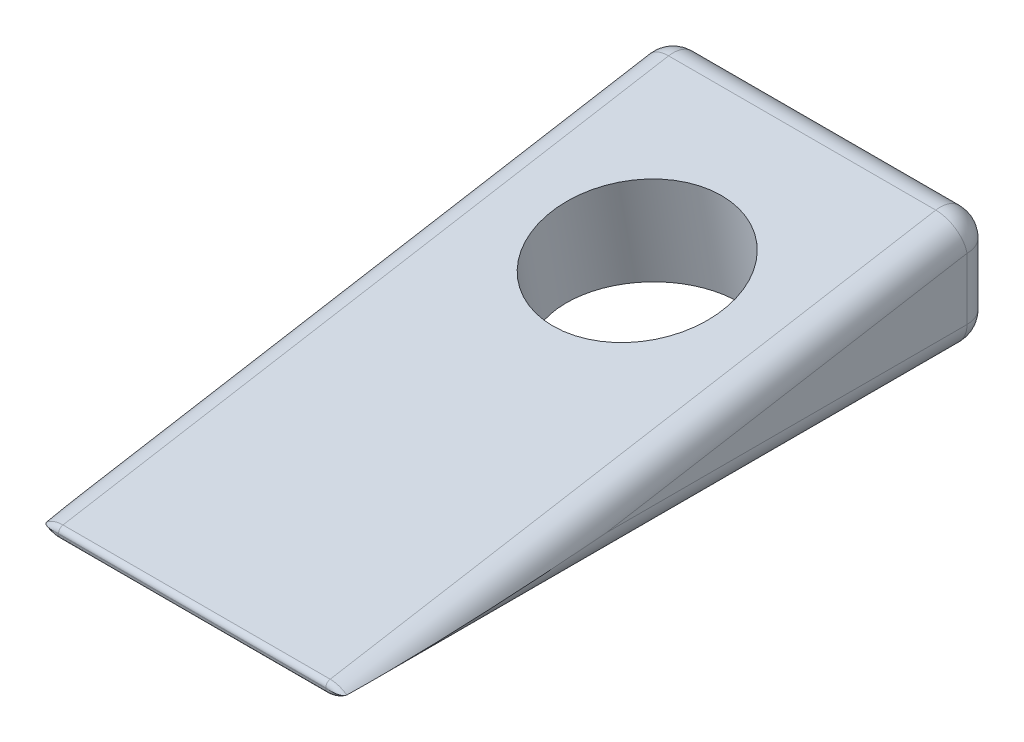
SolidWorks part; units mm, degrees
ref_plane "Front Plane" through (0, 0, 0) normal (0, 0, 1) x (1, 0, 0)
ref_plane "Top Plane" through (0, 0, 0) normal (0, 1, 0) x (1, 0, 0)
ref_plane "Right Plane" through (0, 0, 0) normal (1, 0, 0) x (0, 0, -1)
sketch "Sketch1" plane through (0, 0, 0) normal (0, 1, 0) x (1, 0, 0)
  line L1 (-4.7625, -9.525) -> (4.7625, -9.525)
  line L2 (-4.7625, -9.525) -> (-4.7625, 9.525)
  line L3 (-4.7625, 9.525) -> (4.7625, 9.525)
  line L4 (4.7625, -9.525) -> (4.7625, 9.525)
  line L5 (-4.7625, -9.525) -> (4.7625, 9.525) construction
  line L6 (-4.7625, 9.525) -> (4.7625, -9.525) construction
  point P0 (0, 0)
  dimension "D1" = 19.05
  dimension "D2" = 9.525
extrude "Boss-Extrude1" add sketch "Sketch1" along normal blind 6.35
sketch "Sketch4" plane through (-4.7625, 0, 0) normal (-1, 0, 0) x (0, 0, 1)
  line L1 (9.525, 6.35) -> (9.525, 0) construction
  line L2 (-59.4387, 12.0907) -> (46.9704, -6.0836) construction
  line L3 (9.525, 0.3119) -> (-9.525, 3.5656)
  line L4 (-9.525, 6.35) -> (-9.525, 0) construction
  line L7 (9.525, 0.3119) -> (9.525, 6.35)
  line L8 (9.525, 6.35) -> (-9.525, 6.35)
  line L9 (-9.525, 6.35) -> (-9.525, 3.5656)
extrude "Cut-Extrude4" cut sketch "Sketch4" against normal through all both and the other way through all
sketch "Sketch7" plane through (0, 1.9111, 0.162) normal (0, -0.9857, -0.1684) x (1, 0, 0)
  circle A0 centre (0, -3.9144) radius 2.54
  ellipse E0 centre (0, -3.9144) end of major axis (-2.1, -3.9144) minor radius 2.07 (-2.1, -3.9144) -> (2.1, -3.9144) ccw construction
  point P2 (0, -2.8799)
  dimension "D2" = 5.08
extrude "Cut-Extrude6" cut sketch "Sketch7" against normal through all both and the other way through all
fillet "Fillet2" radius 0.7937 8 edges at (4.7625, 0, 0) (4.7625, 1.9388, 0) (0, 0, -9.525) (4.7625, 1.7828, -9.525) (0, 3.5656, -9.525) (-4.7625, 0, 0) (-4.7625, 1.7828, -9.525) (-4.7625, 1.9388, 0)
fillet "Fillet3" radius 0.1588 6 edges at (-4.2166, 0.0397, 9.525) (4.2166, 0.0397, 9.525) (4.2166, 0.2716, 9.525) (-4.2166, 0.2716, 9.525) (0, 0, 9.525) (0, 0.3119, 9.525)
